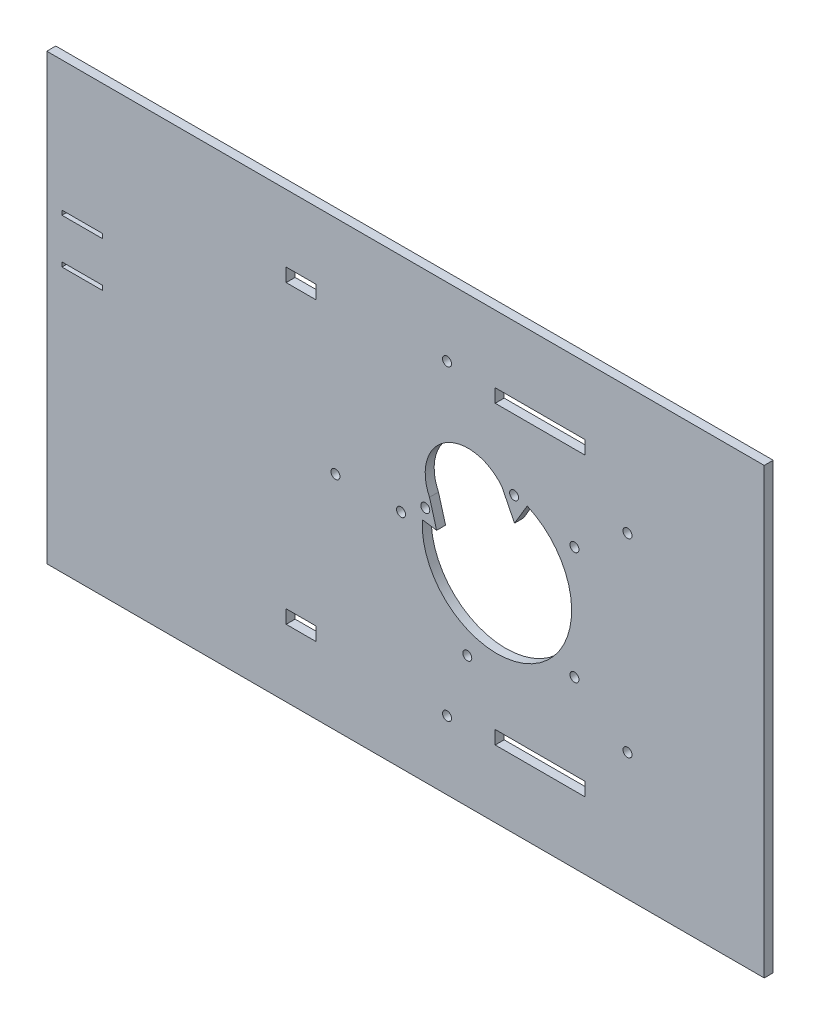
SolidWorks part; units mm, degrees
ref_plane "Front Plane" through (0, 0, 0) normal (0, 0, 1) x (1, 0, 0)
ref_plane "Top Plane" through (0, 0, 0) normal (0, 1, 0) x (1, 0, 0)
ref_plane "Right Plane" through (0, 0, 0) normal (1, 0, 0) x (0, 0, -1)
sketch "Sketch1" plane through (0, 0, 0) normal (0, 0, 1) x (1, 0, 0)
  line L0 (-120.0004, 74.2497) -> (-120.0004, -74.2497)
  line L1 (-120.0004, -74.2497) -> (120.0004, -74.2497)
  line L2 (120.0004, -74.2497) -> (120.0004, 74.2497)
  line L3 (120.0004, 74.2497) -> (-120.0004, 74.2497)
  line L4 (-114.931, 29.2525) -> (-101.4295, 29.2525)
  line L5 (-114.931, 30.7526) -> (-101.4295, 30.7526)
  line L6 (-114.931, 15.751) -> (-101.4295, 15.751)
  line L7 (-114.931, 14.2498) -> (-101.4295, 14.2498)
  line L8 (-39.9319, 51.7498) -> (-39.9319, 47.2493)
  line L9 (-39.9319, 47.2493) -> (-30.0013, 47.2493)
  line L10 (-30.0013, 47.2493) -> (-30.0013, 51.7498)
  line L11 (-30.0013, 51.7498) -> (-39.9319, 51.7498)
  line L12 (29.9987, 51.7498) -> (29.9987, 47.2493)
  line L13 (29.9987, 47.2493) -> (59.9984, 47.2493)
  line L14 (59.9984, 47.2493) -> (59.9984, 51.7498)
  line L15 (59.9984, 51.7498) -> (29.9987, 51.7498)
  line L16 (-39.9319, -47.2483) -> (-30.0013, -47.2483)
  line L17 (-30.0013, -47.2483) -> (-30.0013, -51.7488)
  line L18 (-30.0013, -51.7488) -> (-39.9319, -51.7488)
  line L19 (-39.9319, -51.7488) -> (-39.9319, -47.2483)
  line L20 (30.0002, -47.2483) -> (60.0005, -47.2483)
  line L21 (60.0005, -47.2483) -> (60.0005, -51.7488)
  line L22 (60.0005, -51.7488) -> (30.0002, -51.7488)
  line L23 (30.0002, -51.7488) -> (30.0002, -47.2483)
  line L24 (-101.4295, 29.2525) -> (-101.4295, 30.7526)
  line L25 (-114.931, 30.7526) -> (-114.931, 29.2525)
  line L26 (-114.931, 15.751) -> (-114.931, 14.2498)
  line L27 (-101.4295, 15.751) -> (-101.4295, 14.2498)
  circle A0 centre (30.5702, 0.0013) radius 25
  dimension "D2" = 50
  dimension "D1" = 240.0009
extrude "Boss-Extrude2" add sketch "Sketch1" along normal blind 3
sketch "Sketch5" plane through (0, 0, 3) normal (0, 0, 1) x (1, 0, 0)
  circle A0 centre (30.5702, 0.0013) radius 54
  circle A1 centre (-23.4298, 0.0013) radius 1.5
  circle A2 centre (13.8833, 51.3583) radius 1.5
  circle A3 centre (74.2571, 31.7417) radius 1.5
  circle A4 centre (74.2571, -31.7391) radius 1.5
  circle A5 centre (13.8833, -51.3558) radius 1.5
  point P15 (30.5702, 0.0013)
  dimension "D1" = 5
extrude "Cut-Extrude4" cut sketch "Sketch5" against normal blind 10 contours A1 | A2 | A3 | A4 | A5
sketch "Sketch6" plane through (0, 0, 3) normal (0, 0, 1) x (1, 0, 0)
  circle A0 centre (30.5702, 0.0013) radius 32.0702
  circle A1 centre (-1.5, 0.0013) radius 1.5
  circle A2 centre (20.66, -30.4993) radius 1.5
  circle A3 centre (56.5156, -18.8491) radius 1.5
  circle A4 centre (56.5156, 18.8517) radius 1.5
  circle A5 centre (20.66, 30.5019) radius 1.5
  point P17 (30.5702, 0.0013)
  dimension "D1" = 5
extrude "Cut-Extrude5" cut sketch "Sketch6" against normal blind 10 contours A1 | A2 | A3 | A4
sketch "Sketch9" plane through (0, 0, 3) normal (0, 0, 1) x (1, 0, 0)
  line L0 (30.5702, 0.0013) -> (29.7765, 1.2741) construction
  line L1 (25.279, 8.4867) -> (21.046, 15.2751) construction
  line L2 (17.3421, 21.2149) -> (43.7983, -21.2123) construction
  line L3 (25.279, 8.4867) -> (21.046, 15.2751) construction
  line L4 (21.046, 15.2751) -> (6.1965, 6.0154) construction
  line L5 (6.1965, 6.0154) -> (35.8955, 24.5348) construction
  line L6 (42.529, 23.914) -> (3.4467, 0.228)
  circle A0 centre (30.5702, 0.0013) radius 10
  circle A1 centre (30.5702, 0.0013) radius 25 construction
  circle A2 centre (25.279, 8.4867) radius 8.5
  arc A3 (42.529, 23.914) -> (3.4467, 0.228) centre (21.046, 15.2751) ccw
  circle A4 centre (21.046, 15.2751) radius 14.5
  dimension "D1" = 15
  dimension "D2" = 17
  dimension "D3" = 8
  dimension "D4" = 17.5
  dimension "D5" = 35
extrude "Cut-Extrude6" cut sketch "Sketch9" against normal blind 10 contours A4
sketch "Sketch13" plane through (0, 0, 3) normal (0, 0, 1) x (1, 0, 0)
  line L0 (32.2445, 24.2147) -> (36.4646, 15.7366)
  line L1 (36.4646, 15.7366) -> (45.0058, 30.0467)
  line L2 (-2.6896, 2.5867) -> (10.3964, 0.624)
  line L3 (10.3964, 0.624) -> (8.0115, 9.1038)
  arc A0 (45.0058, 30.0467) -> (-2.6896, 2.5867) centre (29.0903, 2.5392) ccw
  arc A1 (32.2445, 24.2147) -> (8.085, 8.9269) centre (20.9521, 15.3265) ccw
  circle A2 centre (36.3114, 23.7799) radius 1.5
  circle A3 centre (6.6123, 5.2605) radius 1.5
  arc M1 (7.5956, 9.8586) -> (31.8287, 24.9696) centre (21.046, 15.2751) cw
  arc M2 (31.8287, 24.9696) -> (7.5956, 9.8586) centre (30.5702, 0.0013) cw
extrude "Boss-Extrude4" add sketch "Sketch13" against normal blind 3 contours A3 L2 L3 A1 L0 L1 A2 M2 M1 region at (8.7737, 4.7082, 3)
sketch "Sketch14" plane through (0, 0, 3) normal (0, 0, 1) x (1, 0, 0)
  circle A0 centre (36.3114, 23.7799) radius 1.5
  circle A1 centre (6.6123, 5.2605) radius 1.5
extrude "Cut-Extrude7" cut sketch "Sketch14" against normal blind 3
